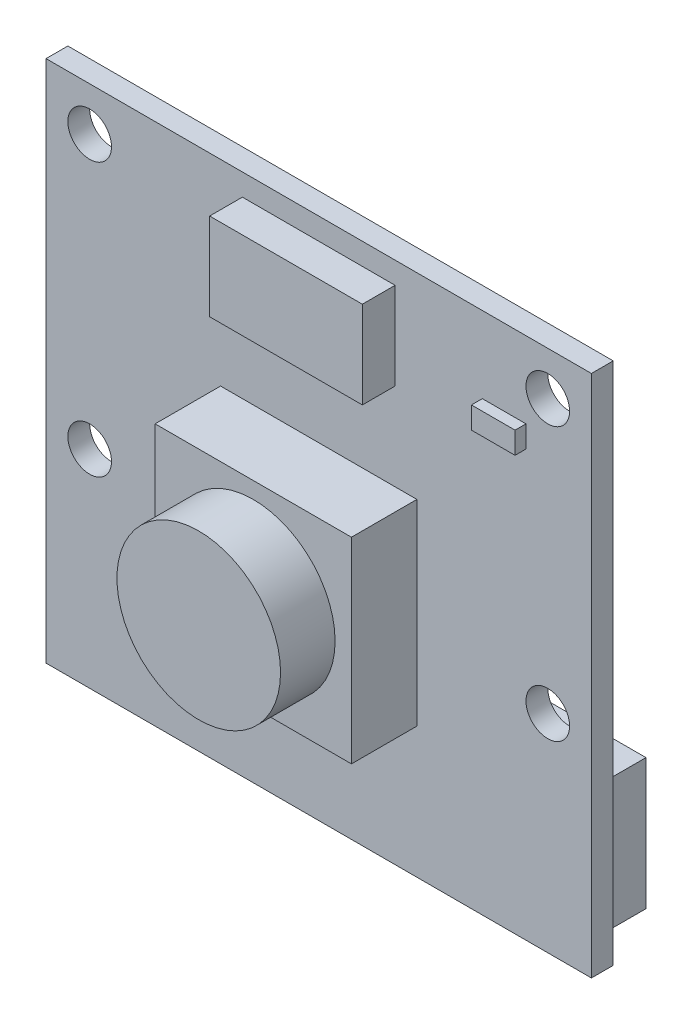
SolidWorks part; units mm, degrees
ref_plane "Alzado" through (0, 0, 0) normal (0, 0, 1) x (1, 0, 0)
ref_plane "Planta" through (0, 0, 0) normal (0, 1, 0) x (1, 0, 0)
ref_plane "Vista lateral" through (0, 0, 0) normal (1, 0, 0) x (0, 0, -1)
sketch "Croquis1" plane through (0, 0, 0) normal (0, 0, 1) x (1, 0, 0)
  line L0 (0, 0) -> (0, 10.5) construction
  line L1 (-12.5, -10.5) -> (12.5, -10.5)
  line L2 (-12.5, -10.5) -> (-12.5, 13.5)
  line L3 (-12.5, 13.5) -> (12.5, 13.5)
  line L4 (12.5, -10.5) -> (12.5, 13.5)
  line L5 (-4.5, -4.5) -> (4.5, -4.5)
  line L6 (-4.5, -4.5) -> (-4.5, 4.5)
  line L7 (-4.5, 4.5) -> (4.5, 4.5)
  line L8 (4.5, -4.5) -> (4.5, 4.5)
  line L9 (-4.5, -4.5) -> (4.5, 4.5) construction
  line L10 (-4.5, 4.5) -> (4.5, -4.5) construction
  line L12 (-3.5, 8.5) -> (3.5, 8.5)
  line L13 (-3.5, 8.5) -> (-3.5, 12.5)
  line L14 (-3.5, 12.5) -> (3.5, 12.5)
  line L15 (3.5, 8.5) -> (3.5, 12.5)
  line L16 (-3.5, 8.5) -> (3.5, 12.5) construction
  line L17 (-3.5, 12.5) -> (3.5, 8.5) construction
  line L18 (7.5, 9) -> (9.5, 9)
  line L19 (7.5, 9) -> (7.5, 10)
  line L20 (7.5, 10) -> (9.5, 10)
  line L21 (9.5, 9) -> (9.5, 10)
  line L22 (7.5, 9) -> (9.5, 10) construction
  line L23 (7.5, 10) -> (9.5, 9) construction
  circle A0 centre (-10.5, 11.5) radius 1
  circle A1 centre (10.5, 11.5) radius 1
  circle A2 centre (-10.5, -1) radius 1
  circle A3 centre (10.5, -1) radius 1
  point P4 (0, 0)
  point P16 (8.5, 9.5)
  dimension "D14" = 2
  dimension "D15" = 2
  dimension "D1" = 25
  dimension "D2" = 24
  dimension "D3" = 9
  dimension "D4" = 9
  dimension "D5" = 6
  dimension "D6" = 8
  dimension "D7" = 7
  dimension "D8" = 4
  dimension "D9" = 1
  dimension "D10" = 4
  dimension "D11" = 4
  dimension "D12" = 2
  dimension "D13" = 1
  dimension "D16" = 2
  dimension "D17" = 12.5
  dimension "D18" = 2
extrude "Saliente-Extruir1" add sketch "Croquis1" along normal blind 1 contours L1 L4 L3 L2 A3 A2 A1 A0 L21 L18 L19 L20 L15 L12 L13 L14 L8 L5 L6 L7 | L5 L8 L7 L6 | L12 L15 L14 L13 | L18 L21 L20 L19 region at (-12.1534, 1.5, 0) region at (0, 0, 0) region at (0, 10.5, 0) region at (8.5, 9.5, 0)
extrude "Saliente-Extruir2" add sketch "Croquis1<3>" along normal blind 1.5 contours L18 L21 L20 L19 region at (8.5, 9.5, 0)
sketch "Croquis1<3>" plane through (0, 0, 0) normal (0, 0, 1) x (1, 0, 0) same geometry as "Croquis1"
extrude "Saliente-Extruir3" add sketch "Croquis1<4>" along normal blind 2.5 contours L12 L15 L14 L13 region at (0, 10.5, 0)
sketch "Croquis1<4>" plane through (0, 0, 0) normal (0, 0, 1) x (1, 0, 0) same geometry as "Croquis1"
extrude "Saliente-Extruir4" add sketch "Croquis1<5>" along normal blind 4 contours L5 L8 L7 L6 region at (0, 0, 0)
sketch "Croquis1<5>" plane through (0, 0, 0) normal (0, 0, 1) x (1, 0, 0) same geometry as "Croquis1"
sketch "Croquis3" plane through (0, 0, 4) normal (0, 0, 1) x (1, 0, 0)
  circle A0 centre (0, 0) radius 3.75
  dimension "D1" = 7.5
extrude "Saliente-Extruir5" add sketch "Croquis3" along normal blind 2.5
sketch "Croquis4" plane through (0, 0, 0) normal (0, 0, -1) x (-1, 0, 0)
  line L0 (12.5, -10.5) -> (-12.5, -10.5) construction
  line L1 (-11, -10.5) -> (11, -10.5)
  line L2 (-11, -10.5) -> (-11, -4.5)
  line L3 (-11, -4.5) -> (11, -4.5)
  line L4 (11, -10.5) -> (11, -4.5)
  point P6 (0, -10.5)
  dimension "D1" = 22
  dimension "D2" = 6
extrude "Saliente-Extruir6" add sketch "Croquis4" along normal blind 3
scale "Scale1" scale about origin uniform scaling yes scale factor 1.3
